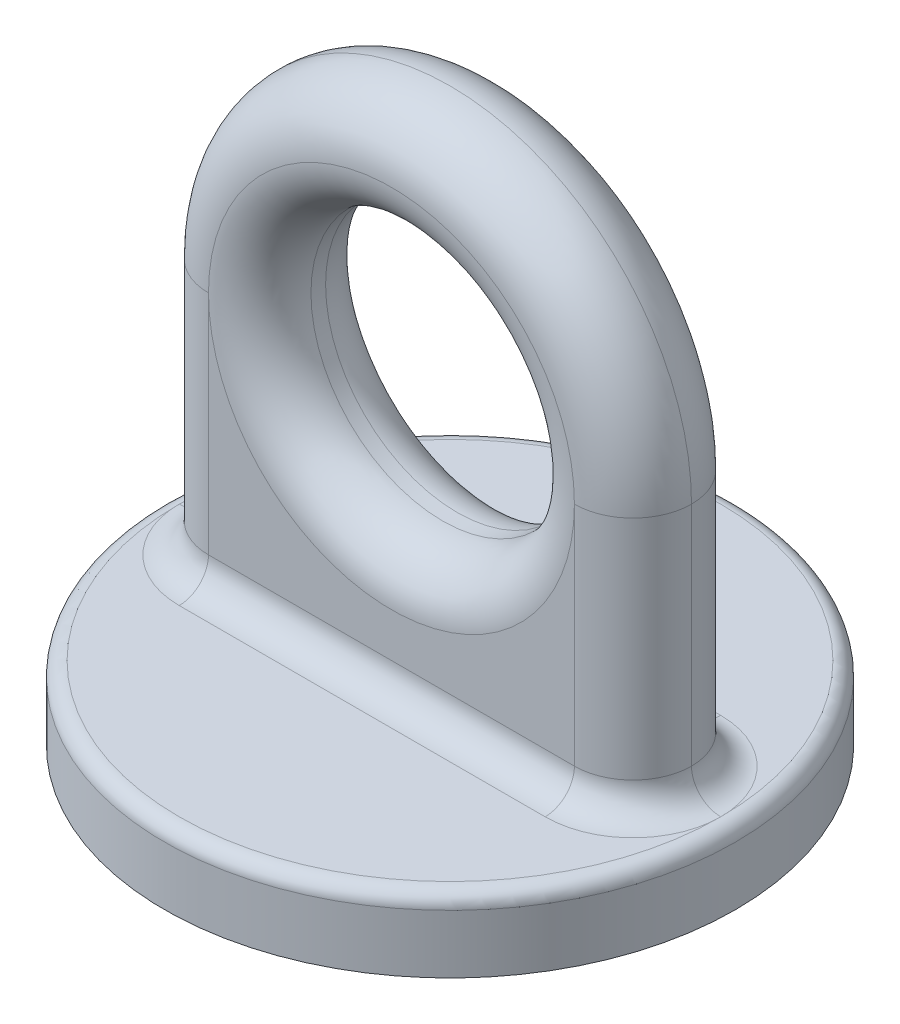
SolidWorks part; units mm, degrees
ref_plane "Front Plane" through (0, 0, 0) normal (0, 0, 1) x (1, 0, 0)
ref_plane "Top Plane" through (0, 0, 0) normal (0, 1, 0) x (1, 0, 0)
ref_plane "Right Plane" through (0, 0, 0) normal (1, 0, 0) x (0, 0, -1)
sketch "Sketch2" plane through (0, 0, 0) normal (0, 0, 1) x (1, 0, 0)
  line L0 (55, 0) -> (-55, 0) construction
  line L1 (0, 6.35) -> (-24.765, 6.35)
  line L2 (0, 6.35) -> (0, 0)
  line L3 (0, 0) -> (-24.765, 0)
  line L4 (-24.765, 6.35) -> (-24.765, 0)
  line L5 (0, -55) -> (0, 55) construction
  line L6 (0, 6.35) -> (0, 0) construction
  dimension "D1" = 24.765
  dimension "D2" = 6.35
revolve "Revolved Base" add sketch "Sketch2" angle 360 about L6
sketch "Sketch3" plane through (0, 0, 0) normal (0, 0, 1) x (1, 0, 0)
  line L0 (-20.955, 6.35) -> (20.955, 6.35)
  line L1 (20.955, 6.35) -> (20.955, 28.575)
  line L2 (-20.955, 28.575) -> (-20.955, 6.35)
  line L3 (24.765, 6.35) -> (-24.765, 6.35) construction
  line L4 (0, -3.4925) -> (0, 3.4925) construction
  arc A0 (20.955, 28.575) -> (-20.955, 28.575) centre (0, 28.575) ccw
  point P5 (0, 49.53)
  point P10 (0, 6.35)
  dimension "D1" = 41.91
  dimension "D2" = 43.18
extrude "Extruded Vertical Plate" add sketch "Sketch3" along normal blind 5.08 and the other way blind 5.08
hole_wizard "0.9D Eye Hole" positions "Sketch4" profile "Sketch5" hole size "1/16" standard "ANSI Inch" end condition through all
sketch "Sketch4" plane through (0, 0, 5.08) normal (0, 0, 1) x (1, 0, 0)
  point P0 (0, 28.575)
sketch "Sketch5" plane through (0, 28.575, 5.08) normal (1, 0, 0) x (0, -1, 0)
  line L0 (0, 0) -> (0, 29.845)
  line L1 (0, 29.845) -> (11.43, 29.845)
  line L2 (11.43, 29.845) -> (11.43, 0)
  line L5 (11.43, 0) -> (0, 0)
  line L11 (0, -6.35) -> (0, 107.95) construction
  dimension "Thru Hole Dia." = 22.86
  dimension "Thru Hole Depth" = 29.845
fillet "Edge Fillet" radius 5.08 6 edges at (20.955, 17.4625, -5.08) (-20.955, 17.4625, -5.08) (20.955, 17.4625, 5.08) (-20.955, 17.4625, 5.08) (0, 49.53, -5.08) (0, 49.53, 5.08)
fillet "Connecting Fillet" radius 2.54 6 edges at (-19.4671, 6.35, 3.5921) (-19.4671, 6.35, -3.5921) (0, 6.35, -5.08) (19.4671, 6.35, -3.5921) (19.4671, 6.35, 3.5921) (0, 6.35, 5.08)
fillet "Base Fillet" radius 1.27 1 edges at (-24.765, 6.35, 0)
sketch "Sketch8" plane through (0, 0, 0) normal (0, 0, 1) x (1, 0, 0)
  line L0 (-22.225, 0) -> (-21.59, 3.683)
  line L1 (27.2415, 0) -> (-27.2415, 0) construction
  line L2 (-21.59, 3.683) -> (-7.62, 3.683)
  line L3 (-7.62, 3.683) -> (-6.35, 0)
  line L4 (-6.35, 0) -> (-22.225, 0)
  line L5 (-24.765, 5.08) -> (-24.765, 0) construction
  line L6 (0, 0) -> (0, 48.9934) construction
  line L7 (0, -27.2415) -> (0, 27.2415) construction
  dimension "D1" = 2.54
  dimension "D2" = 3.175
  dimension "D3" = 13.97
  dimension "D4" = 6.35
  dimension "D5" = 3.683
revolve "Under Base Revolved Cut" cut sketch "Sketch8" angle 360 about L6
hole_wizard "0.325D Bottom Hole" positions "Sketch9" profile "Sketch10" hole size "1/16" standard "ANSI Inch"
sketch "Sketch9" plane through (0, 0, 0) normal (0, -1, 0) x (-1, 0, 0)
  point P0 (0, 0)
sketch "Sketch10" plane through (0, 0, 0) normal (1, 0, 0) x (0, 0, -1)
  line L0 (0, 0) -> (0, 12.7)
  line L1 (0, 12.7) -> (4.1275, 12.7)
  line L2 (4.1275, 12.7) -> (4.1275, 0)
  line L5 (4.1275, 0) -> (0, 0)
  line L10 (0, 12.7) -> (-4.1275, 12.7) construction
  line L11 (0, -6.35) -> (0, 107.95) construction
  dimension "Hole Dia." = 8.255
  dimension "Hole Depth" = 12.7
  dimension "Drill Angle" = 180
fillet "Eye Fillet" radius 4.445 2 edges at (11.43, 28.575, 5.08) (11.43, 28.575, -5.08)
thread "0.325D Bottom Hole Thread" pitch 1.5875 method cut profile "Thread Profile1" start angle 0, offset 0, length 0, pitch 1.5875, diameter 8.255
ref_plane "Plane1" through (-4.1275, 12.7, 0) normal (0, 0, 1) x (-1, 0, 0)
sketch "Thread Profile1" plane through (-4.1275, 12.7, 0) normal (0, 0, 1) x (-1, 0, 0)
  line L0 (0, 0) -> (0, 1.5875) construction
  line L1 (0, 0) -> (0.8593, 0.4961)
  line L2 (0.8593, 0.4961) -> (0.8593, 0.6945)
  line L3 (0.8593, 0.6945) -> (0, 1.1906)
  line L4 (0.8593, 0.5953) -> (0, 0.5953) construction
  line L11 (0, 0) -> (0, 1.1906)
  point P2 (0, 0)
  dimension "Pitch" = 1.5875
  dimension "Profile_Angle" = 60
  dimension "Profile_Land" = 0.1984
  dimension "Profile_Height" = 0.8593
